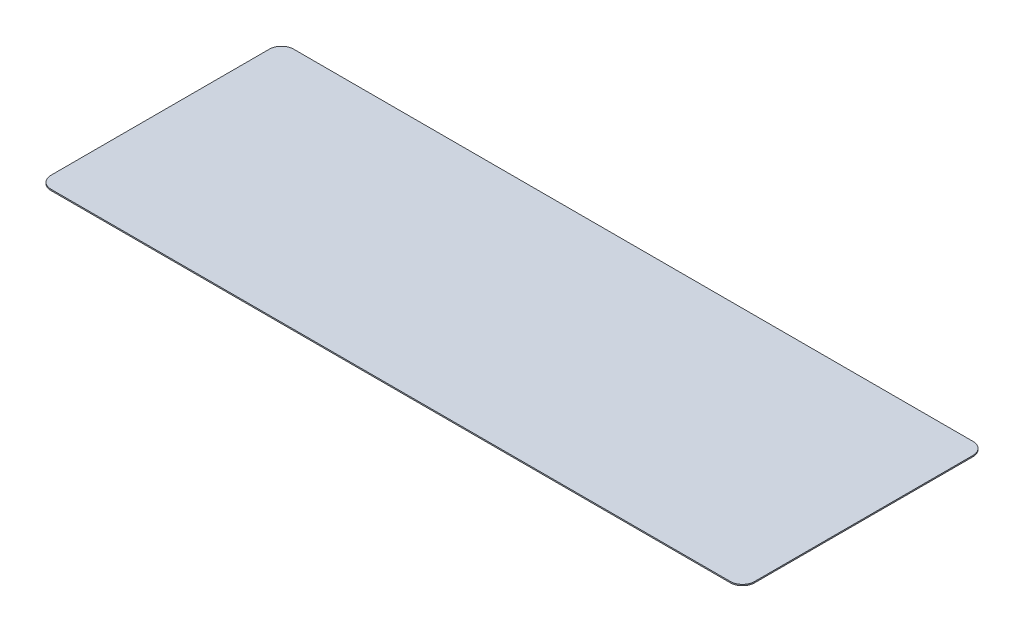
SolidWorks part; units mm, degrees
material "AISI 1020 Steel, Cold Rolled"
ref_plane "Front Plane" through (0, 0, 0) normal (0, 0, 1) x (1, 0, 0)
ref_plane "Top Plane" through (0, 0, 0) normal (0, 1, 0) x (1, 0, 0)
ref_plane "Right Plane" through (0, 0, 0) normal (1, 0, 0) x (0, 0, -1)
sketch "Sketch1" plane through (0, 0, 0) normal (0, 1, 0) x (1, 0, 0)
  line L1 (-290, 100) -> (290, 100)
  line L2 (-290, 100) -> (-290, -100)
  line L3 (-290, -100) -> (290, -100)
  line L4 (290, 100) -> (290, -100)
  line L5 (-290, 100) -> (290, -100) construction
  line L6 (-290, -100) -> (290, 100) construction
  point P0 (0, 0)
  dimension "D1" = 580
  dimension "D2" = 200
extrude "Boss-Extrude1" add sketch "Sketch1" along normal blind 1
fillet "Fillet1" radius 10 4 edges at (-290, 0.5, 100) (290, 0.5, 100) (290, 0.5, -100) (-290, 0.5, -100)
